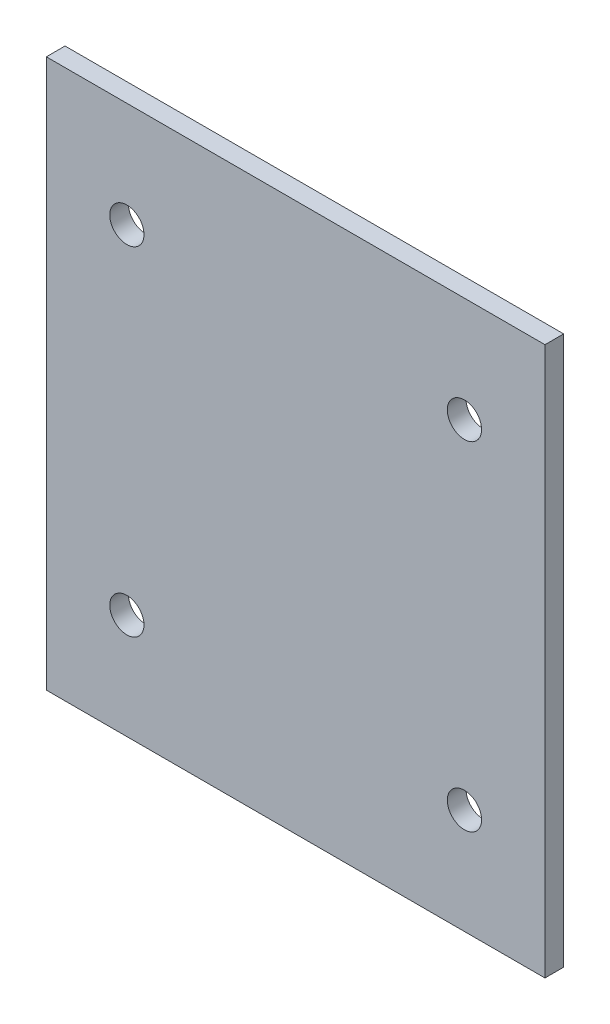
SolidWorks part; units mm, degrees
material "6061 Alloy"
ref_plane "Front Plane" through (0, 0, 0) normal (0, 0, 1) x (1, 0, 0)
ref_plane "Top Plane" through (0, 0, 0) normal (0, 1, 0) x (1, 0, 0)
ref_plane "Right Plane" through (0, 0, 0) normal (1, 0, 0) x (0, 0, -1)
sketch "Sketch1" plane through (0, 0, 0) normal (0, 0, 1) x (1, 0, 0)
  line L1 (-127, -139.7) -> (127, -139.7)
  line L2 (-127, -139.7) -> (-127, 139.7)
  line L3 (-127, 139.7) -> (127, 139.7)
  line L4 (127, -139.7) -> (127, 139.7)
  line L5 (-127, -139.7) -> (127, 139.7) construction
  line L6 (-127, 139.7) -> (127, -139.7) construction
  point P0 (0, 0)
  dimension "D1" = 279.4
  dimension "D2" = 254
extrude "Boss-Extrude1" add sketch "Sketch1" along normal blind 9.525
hole_wizard "5/8 Clearance Hole1" positions "Sketch2" profile "Sketch3" hole size "5/8" standard "ANSI Inch" end condition through all
sketch "Sketch2" plane through (0, 0, 9.525) normal (0, 0, 1) x (1, 0, 0)
  line L0 (-127, -139.7) -> (127, -139.7) construction
  line L1 (127, -139.7) -> (127, 139.7) construction
  line L2 (0, -139.7) -> (0, 139.7) construction
  line L3 (127, 139.7) -> (-127, 139.7) construction
  point P0 (-85.979, 86.106)
  point P3 (-85.979, -86.106)
  point P5 (85.979, -86.106)
  point P7 (85.979, 86.106)
  dimension "D1" = 53.594
  dimension "D2" = 225.806
  dimension "D3" = 41.021
  dimension "D4" = 212.979
  dimension "D5" = 171.958
sketch "Sketch3" plane through (-85.979, 86.106, 9.525) normal (1, 0, 0) x (0, -1, 0)
  line L0 (0, 0) -> (0, 9.525)
  line L1 (0, 9.525) -> (8.7249, 9.525)
  line L2 (8.7249, 9.525) -> (8.7249, 0)
  line L5 (8.7249, 0) -> (0, 0)
  line L11 (0, -6.35) -> (0, 107.95) construction
  dimension "Thru Hole Dia." = 17.4498
  dimension "Thru Hole Depth" = 9.525
